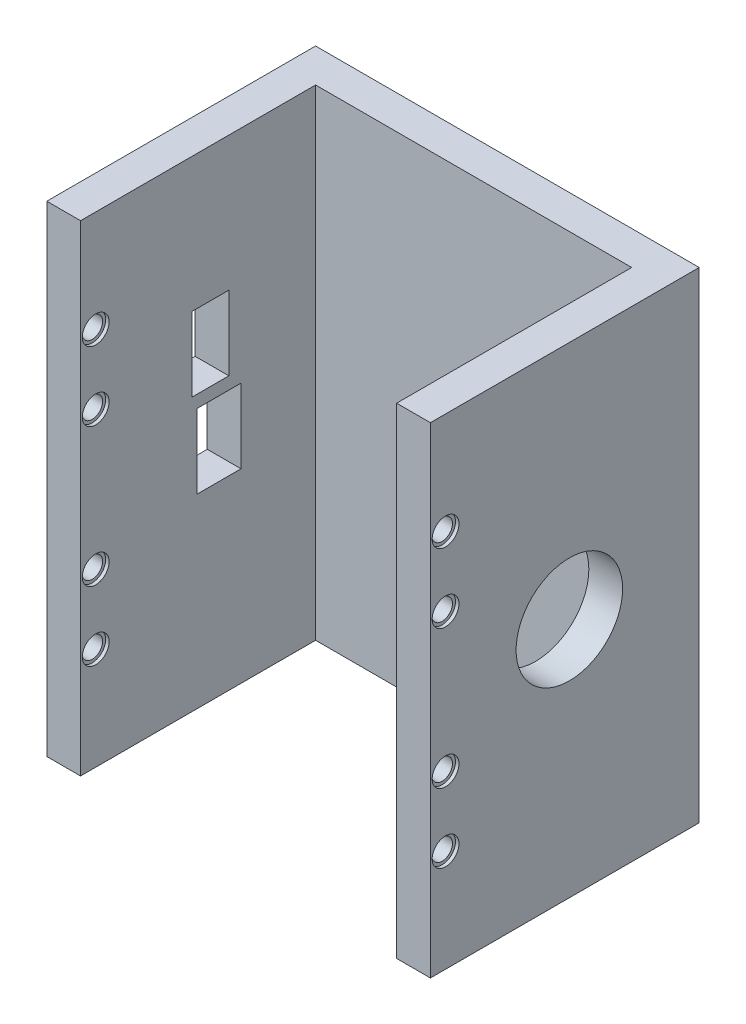
SolidWorks part; units mm, degrees
ref_plane "Front Plane" through (0, 0, 0) normal (0, 0, 1) x (1, 0, 0)
ref_plane "Top Plane" through (0, 0, 0) normal (0, 1, 0) x (1, 0, 0)
ref_plane "Right Plane" through (0, 0, 0) normal (1, 0, 0) x (0, 0, -1)
sketch "Sketch1" plane through (0, 0, 0) normal (1, 0, 0) x (0, 0, -1)
  line L1 (0, 0) -> (55.1, 0)
  line L2 (0, 0) -> (0, 111.1)
  line L3 (0, 111.1) -> (55.1, 111.1)
  line L4 (55.1, 0) -> (55.1, 111.1)
  dimension "D1" = 55.1
  dimension "D2" = 111.1
extrude "Boss-Extrude1" add sketch "Sketch1" along normal blind 7.8
sketch "Sketch2" plane through (0, 0, 0) normal (-1, 0, 0) x (0, 0, 1)
  line L0 (0, 111.1) -> (-47.3, 111.1) construction
  line L1 (-55.1, 111.1) -> (0, 111.1) construction
  line L3 (-47.3, 111.1) -> (-55.1, 111.1)
  line L4 (-47.3, 111.1) -> (-47.3, 0)
  line L5 (-47.3, 0) -> (-55.1, 0)
  line L6 (-55.1, 111.1) -> (-55.1, 0)
  dimension "D1" = 7.8
extrude "Boss-Extrude2" add sketch "Sketch2" along normal blind 73.025 contours L4 L3 L6 L5
sketch "Sketch4" plane through (-73.025, 0, 0) normal (-1, 0, 0) x (0, 0, 1)
  line L1 (-55.1, 111.1) -> (0, 111.1)
  line L2 (-55.1, 111.1) -> (-55.1, 0)
  line L3 (-55.1, 0) -> (0, 0)
  line L4 (0, 111.1) -> (0, 0)
extrude "Boss-Extrude3" add sketch "Sketch4" along normal blind 7.8 contours L2 L1 L4 L3
ref_plane "Plane1" through (-36.5125, 0, 0) normal (-1, 0, 0) x (0, 0, 1)
sketch "Sketch7" plane through (0, 0, 0) normal (0, 0, 1) x (1, 0, 0)
  line L4 (0, 0) -> (7.8, 0)
  line L5 (7.8, 0) -> (7.8, 111.1)
  line L6 (7.8, 111.1) -> (0, 111.1)
  line L7 (0, 111.1) -> (0, 0)
  line L8 (0, 0) -> (7.8, 0)
  line L10 (7.8, 111.1) -> (0, 111.1)
  line L11 (0, 111.1) -> (0, 0)
  line L16 (7.8, 0) -> (7.8, 111.1)
  dimension "D1" = 0
extrude "Boss-Extrude4" add sketch "Sketch7" along normal blind 7 contours L8 L16 L10 L11
sketch "Sketch8" plane through (7.8, 0, 0) normal (1, 0, 0) x (0, 0, -1)
  line L0 (-7, 0) -> (0, 0) construction
  line L3 (-3.5, 30.1777) -> (-3.5, 16.5296) construction
  line L4 (-7, 0) -> (-7, 111.1) construction
  line L5 (0, 0) -> (0, 111.1) construction
  circle A0 centre (-3.5, 23.6) radius 3.1
  circle A1 centre (-3.5, 23.6) radius 2.4
  circle A2 centre (-3.5, 39.6) radius 3.1
  circle A3 centre (-3.5, 39.6) radius 2.4
  circle A4 centre (-3.5, 87.6) radius 3.1
  circle A5 centre (-3.5, 87.6) radius 2.4
  circle A6 centre (-3.5, 71.6) radius 3.1
  circle A7 centre (-3.5, 71.6) radius 2.4
  dimension "D1" = 6.2
  dimension "D2" = 4.8
  dimension "D5" = 6.2
  dimension "D6" = 4.8
  dimension "D3" = 23.6
  dimension "D4" = 16
  dimension "D7" = 16
  dimension "D8" = 32
extrude "Cut-Extrude4" cut sketch "Sketch8" against normal blind 12.7 contours A5 | A7 | A3 | A1 L3 | L3 A1 region at (7.8, 23.6, 2.4814) region at (7.8, 23.6, 4.5186) region at (7.8, 39.6, 3.5) region at (7.8, 87.6, 3.5) region at (7.8, 71.6, 3.5)
extrude "Cut-Extrude5" cut sketch "Sketch8<4>" against normal blind 0.8 contours A4 | A6 | A2 | A0
sketch "Sketch8<4>" plane through (7.8, 0, 0) normal (1, 0, 0) x (0, 0, -1) same geometry as "Sketch8"
sketch "Sketch9" plane through (0, 0, 7) normal (0, 0, 1) x (1, 0, 0)
  line L0 (3.9, 0) -> (3.9, 111.1) construction
  line L1 (0, 0) -> (7.8, 0) construction
  line L2 (7.8, 111.1) -> (0, 111.1) construction
ref_plane "Plane2" through (3.9, 0, 0) normal (1, 0, 0) x (0, 0, -1)
mirror "Mirror1" about plane through (3.9, 0, 0) normal (1, 0, 0) of "Cut-Extrude5"
mirror "Mirror2" about plane through (-36.5125, 0, 0) normal (-1, 0, 0) of "Cut-Extrude4", "Boss-Extrude4", "Mirror1", "Cut-Extrude5"
sketch "Sketch10" plane through (7.8, 0, 0) normal (1, 0, 0) x (0, 0, -1)
  line L0 (55.1, 0) -> (55.1, 111.1) construction
  line L1 (-7, 0) -> (55.1, 0) construction
  circle A0 centre (25.1, 55.7) radius 12.3
  dimension "D1" = 24.6
  dimension "D2" = 30
  dimension "D3" = 55.7
extrude "Cut-Extrude7" cut sketch "Sketch10" against normal up to surface (7.8 mm away) up to face at (0, 87.6, 0.4)
sketch "Sketch11" plane through (-80.825, 0, 0) normal (-1, 0, 0) x (0, 0, 1)
  line L0 (-55.1, 111.1) -> (-55.1, 0) construction
  line L1 (-26, 78.8) -> (-20, 78.8) construction
  line L2 (-26, 78.8) -> (-26, 64.2) construction
  line L3 (-26, 64.2) -> (-20, 64.2) construction
  line L4 (-20, 78.8) -> (-20, 64.2) construction
  line L5 (-28.8, 58.8) -> (-21.165, 58.8) construction
  line L6 (-28.8, 58.8) -> (-28.8, 44.2) construction
  line L7 (-28.8, 44.2) -> (-21.165, 44.2) construction
  line L8 (-21.165, 58.8) -> (-21.165, 44.2) construction
  line L9 (-55.1, 0) -> (7, 0) construction
  line L10 (-27.27, 80.07) -> (-18.73, 80.07)
  line L11 (-18.73, 80.07) -> (-18.73, 62.93)
  line L12 (-27.27, 62.93) -> (-18.73, 62.93)
  line L13 (-27.27, 80.07) -> (-27.27, 62.93)
  line L14 (-19.895, 60.07) -> (-19.895, 42.93)
  line L15 (-30.07, 42.93) -> (-19.895, 42.93)
  line L16 (-30.07, 60.07) -> (-30.07, 42.93)
  line L17 (-30.07, 60.07) -> (-19.895, 60.07)
  dimension "D1" = 14.6
  dimension "D2" = 6
  dimension "D3" = 29.1
  dimension "D4" = 64.2
  dimension "D5" = 14.6
  dimension "D6" = 7.635
  dimension "D7" = 26.3
  dimension "D8" = 44.2
  dimension "D9" = 1.27
  dimension "D10" = 1.27
extrude "Cut-Extrude8" cut sketch "Sketch11" against normal up to surface (7.8 mm away) contours L10 L11 L12 L13 | L14 L15 L16 L17 up to face at (-73.025, 87.6, 0.4)
